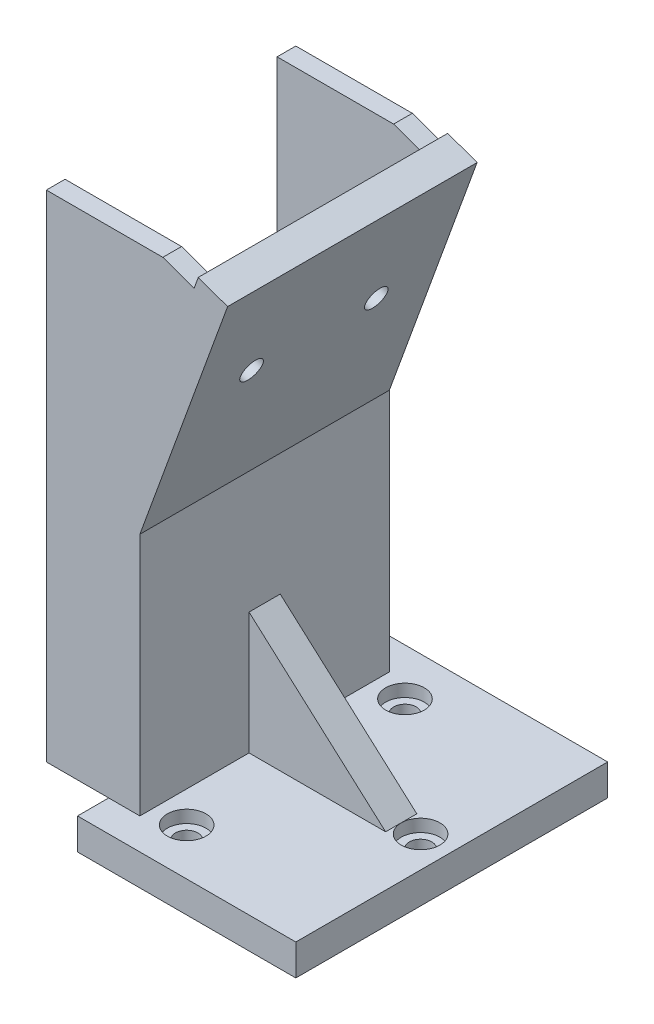
SolidWorks part; units mm, degrees
ref_plane "前视基准面" through (0, 0, 0) normal (0, 0, 1) x (1, 0, 0)
ref_plane "上视基准面" through (0, 0, 0) normal (0, 1, 0) x (1, 0, 0)
ref_plane "右视基准面" through (0, 0, 0) normal (1, 0, 0) x (0, 0, -1)
other "Configuration Table"
sketch "草图1" plane through (0, 0, 0) normal (0, 0, 1) x (1, 0, 0)
  line L0 (0, 0) -> (0, 45)
  line L1 (0, 45) -> (14.3648, 84.4671)
  dimension "D1" = 160
  dimension "D2" = 45
  dimension "D3" = 42
sketch "草图2" plane through (0, 0, 0) normal (0, 1, 0) x (1, 0, 0)
  line L1 (0, 20) -> (5, 20)
  line L2 (0, 20) -> (0, -20)
  line L3 (0, -20) -> (5, -20)
  line L4 (5, 20) -> (5, -20)
  point P4 (0, 0)
  dimension "D1" = 5
  dimension "D2" = 40
sweep "扫描1" add profiles "草图2" path "草图1"
sketch "草图3" plane through (-14.4627, 5.264, 0) normal (-0.9397, 0.342, 0) x (0, 0, 1)
  line L0 (-20, 66.2862) -> (20, 66.2862) construction
  line L1 (-20, 42.2862) -> (-20, 84.2862) construction
  line L2 (20, 42.2862) -> (20, 84.2862) construction
  line L3 (0, 77.3553) -> (0, -49922.6447) construction
  line L4 (-20, 84.2862) -> (20, 84.2862) construction
  line L5 (-10, 66.2862) -> (10, 66.2862) construction
  circle A0 centre (-10, 66.2862) radius 1.8
  circle A1 centre (10, 66.2862) radius 1.8
  point P10 (0, 84.2862)
  point P13 (0, 66.2862)
  dimension "D2" = 3.6
  dimension "D3" = 3.6
  dimension "D1" = 20
  dimension "D4" = 18
extrude "切除-拉伸1" cut sketch "草图3" against normal up to next
sketch "草图6" plane through (0, 0, 0) normal (0, -1, 0) x (1, 0, 0)
  line L0 (5, 20) -> (5, -20) construction
  line L1 (5, 20) -> (35, 20)
  line L2 (5, 20) -> (5, -20)
  line L3 (5, -20) -> (35, -20)
  line L4 (35, 20) -> (35, -20)
  line L5 (0, 20) -> (5, 20) construction
  line L6 (5, -20) -> (19.0633, -20) construction
  dimension "D1" = 30
extrude "凸台-拉伸1" add sketch "草图6" against normal blind 5
sketch "草图8" plane through (0, 0, 0) normal (0, -1, 0) x (1, 0, 0)
  line L0 (5, 20) -> (5, -20) construction
  line L1 (5, 20) -> (5, -20) construction
  line L2 (5, 0) -> (50005, 0) construction
  line L3 (10, 17.5) -> (10, -17.5) construction
  line L4 (10, 0) -> (30, 0) construction
  circle A0 centre (10, 17.5) radius 1.8
  circle A1 centre (10, -17.5) radius 1.8
  circle A2 centre (30, 0) radius 1.8
  point P4 (5, 0)
  point P7 (10, 0)
  dimension "D2" = 3.6
  dimension "D3" = 3.6
  dimension "D6" = 3.6
  dimension "D1" = 35
  dimension "D4" = 5
  dimension "D5" = 20
extrude "切除-拉伸2" cut sketch "草图8" against normal up to next
sketch "草图9" plane through (0, 0, 0) normal (0, -1, 0) x (1, 0, 0)
  line L0 (35, 0) -> (-49965, 0) construction
  line L1 (0, 20) -> (35, 20)
  line L2 (0, 20) -> (0, 25)
  line L3 (0, 25) -> (35, 25)
  line L4 (35, 20) -> (35, 25)
  line L5 (35, -20) -> (35, 20) construction
  line L6 (35, -20) -> (35, -25)
  line L7 (0, -25) -> (35, -25)
  line L8 (0, -20) -> (0, -25)
  line L9 (0, -20) -> (35, -20)
  point P9 (35, 0)
  dimension "D1" = 5
extrude "凸台-拉伸2" add sketch "草图9" against normal up to surface (5 mm away) up to face at (10, 5, 15.7)
sketch "草图10" plane through (0, 5, 0) normal (0, 1, 0) x (1, 0, 0)
  circle A0 centre (10, -17.5) radius 3.1
  circle A1 centre (10, 17.5) radius 3.1
  circle A2 centre (30, 0) radius 3.1
  dimension "D1" = 6.2
  dimension "D2" = 6.2
  dimension "D3" = 6.2
extrude "切除-拉伸3" cut sketch "草图10" against normal blind 2
sketch "草图11" plane through (-14.4627, 5.264, 0) normal (-0.9397, 0.342, 0) x (0, 0, 1)
  circle A0 centre (-10, 66.2862) radius 3.1
  circle A1 centre (10, 66.2862) radius 3.1
  dimension "D1" = 6.2
  dimension "D2" = 6.2
extrude "切除-拉伸4" cut sketch "草图11" against normal blind 2
sketch "草图15" plane through (0, 0, -20) normal (0, 0, -1) x (-1, 0, 0)
  line L0 (-8.6808, 84.4076) -> (-13.6808, 82.5877)
  line L1 (0, 5) -> (10, 5)
  line L2 (0, 5) -> (0, 45)
  line L3 (-8.6808, 84.4076) -> (10, 84.4076)
  line L4 (10, 5) -> (10, 84.4076)
  line L5 (0, 45) -> (-14.3648, 84.4671) construction
  line L6 (-13.6808, 82.5877) -> (0, 45)
  dimension "D1" = 40
  dimension "D2" = 5
  dimension "D3" = 10
extrude "凸台-拉伸4" add sketch "草图15" against normal blind 3
ref_plane "基准面2" through (0, 0, 0) normal (0, 0, -1) x (-1, 0, 0)
mirror "镜向2" about plane through (0, 0, 0) normal (0, 0, -1) of "凸台-拉伸4"
sketch "草图16" plane through (0, 0, 0) normal (0, 0, -1) x (-1, 0, 0)
  line L0 (-14.3648, 84.4671) -> (2.8243, 148.6177)
  line L1 (2.8243, 148.6177) -> (8.1424, 147.1927)
  line L2 (8.1424, 147.1927) -> (-8.6808, 84.4076)
  line L3 (10, 84.4076) -> (-8.6808, 84.4076) construction
  line L4 (-13.6808, 82.5877) -> (-14.3648, 84.4671) construction
  line L5 (-8.6808, 84.4076) -> (-13.6808, 82.5877) construction
  line L6 (-13.6808, 82.5877) -> (-14.3648, 84.4671)
  line L7 (-8.6808, 84.4076) -> (-13.6808, 82.5877)
  dimension "D1" = 65
  dimension "D2" = 75
extrude "凸台-拉伸5" [suppressed] add sketch "草图16" along normal blind 25 and the other way blind 25
sketch "草图17" [suppressed] plane through (34.5194, 9.2494, 0) normal (0.9659, 0.2588, 0) x (0, 0, -1)
  line L1 (-18, 86.371) -> (18, 86.371) construction
  line L2 (0, 144.4076) -> (0, -49855.5924) construction
  line L3 (-25, 144.2847) -> (25, 144.2847) construction
  line L5 (20, 77.871) -> (-20, 77.871) construction
  line L6 (-32.5, 77.871) -> (32.5, 77.871) construction
  line L7 (-32.5, 77.871) -> (-32.5, 142.871) construction
  line L8 (-32.5, 142.871) -> (32.5, 142.871) construction
  line L9 (32.5, 77.871) -> (32.5, 142.871) construction
  line L10 (-32.5, 77.871) -> (32.5, 142.871) construction
  line L11 (-32.5, 142.871) -> (32.5, 77.871) construction
  line L12 (-18, 86.371) -> (-18, 134.371) construction
  line L13 (-18, 134.371) -> (18, 134.371) construction
  line L14 (18, 86.371) -> (18, 134.371) construction
  line L15 (-18, 86.371) -> (18, 134.371) construction
  line L16 (-18, 134.371) -> (18, 86.371) construction
  circle A0 centre (-18, 134.371) radius 1.8
  circle A1 centre (18, 134.371) radius 1.8
  circle A2 centre (18, 86.371) radius 1.8
  circle A3 centre (-18, 86.371) radius 1.8
  point P0 (0, 110.371)
  point P7 (0, 144.2847)
  point P11 (0, 110.371)
  dimension "D3" = 3.6
  dimension "D6" = 3.6
  dimension "D7" = 3.6
  dimension "D1" = 48
  dimension "D2" = 36
  dimension "D4" = 65
  dimension "D5" = 65
extrude "切除-拉伸5" [suppressed] cut sketch "草图17" against normal up to next
sketch "草图18" [suppressed] plane through (29.2012, 7.8244, 0) normal (-0.9659, -0.2588, 0) x (0, 0, 1)
  circle A0 centre (-18, 134.371) radius 3.5
  circle A1 centre (18, 134.371) radius 3.5
  circle A2 centre (18, 86.371) radius 3.5
  circle A3 centre (-18, 86.371) radius 3.5
  dimension "D1" = 7
  dimension "D2" = 7
  dimension "D3" = 7
  dimension "D4" = 7
extrude "切除-拉伸6" [suppressed] cut sketch "草图18" against normal blind 3
sketch "草图19" plane through (0, 0, -17) normal (0, 0, 1) x (1, 0, 0)
  line L0 (12.6547, 79.7686) -> (8.1518, 81.4076)
  line L1 (8.1518, 81.4076) -> (-10, 81.4076)
  line L2 (-10, 84.4076) -> (-10, 81.4076)
  line L3 (13.6808, 82.5877) -> (12.6547, 79.7686)
  line L6 (0, 5) -> (0, 45)
  line L7 (0, 45) -> (13.6808, 82.5877)
  line L9 (8.6808, 84.4076) -> (-10, 84.4076)
  line L10 (-10, 84.4076) -> (-10, 5)
  line L11 (-10, 5) -> (0, 5)
  line L15 (8.6808, 84.4076) -> (-10, 84.4076)
  line L22 (13.6808, 82.5877) -> (8.6808, 84.4076) construction
  line L23 (13.6808, 82.5877) -> (8.6808, 84.4076)
  line L24 (13.6808, 82.5877) -> (8.6808, 84.4076)
  dimension "D1" = 0
  dimension "D2" = 3
extrude "凸台-拉伸6" [suppressed] add sketch "草图19" along normal up to surface (34 mm away)
sketch "草图20" [suppressed] plane through (0, 0, 0) normal (0, 0, -1) x (-1, 0, 0)
  line L0 (10, 84.4076) -> (8.1424, 147.1927)
rib "筋4" [suppressed] sketch "草图20" sketch "草图20" thickness 5 extrusion direction parallel to sketch draft on no parameters "D1"=5
sketch "草图21" plane through (0, 0, 0) normal (0, 0, -1) x (-1, 0, 0)
  line L0 (-5, 24.5592) -> (-26.9, 5)
  line L1 (-5, 5) -> (-5, 44.1184) construction
  line L2 (-35, 5) -> (0, 5) construction
rib "筋5" sketch "草图21" sketch "草图21" thickness 5 extrusion direction parallel to sketch draft on no parameters "D1"=5
